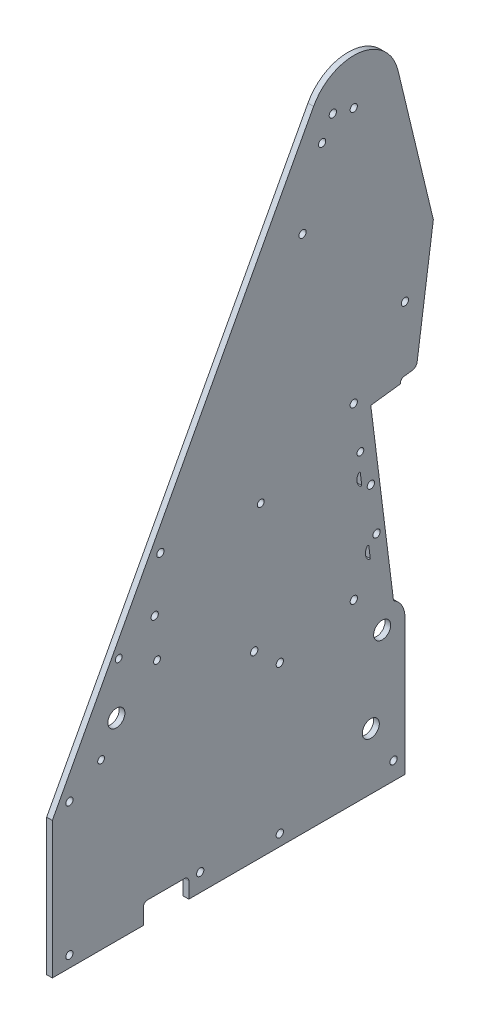
SolidWorks part; units mm, degrees
ref_plane "Front Plane" through (0, 0, 0) normal (0, 0, 1) x (1, 0, 0)
ref_plane "Top Plane" through (0, 0, 0) normal (0, 1, 0) x (1, 0, 0)
ref_plane "Right Plane" through (0, 0, 0) normal (1, 0, 0) x (0, 0, -1)
sketch "Sketch1" plane through (0, 0, 0) normal (1, 0, 0) x (0, 0, -1)
  line L0 (0, 0) -> (0, 76.2)
  line L6 (-19.05, 188.0016) -> (-2.512, 190.0852)
  line L7 (6.4943, 193.62) -> (15.875, 260.35)
  line L8 (15.875, 260.35) -> (-3.8791, 342.4892)
  line L9 (-50.965, 348.5436) -> (-196.85, 76.2)
  line L10 (-196.85, 0) -> (0, 0)
  line L11 (-196.85, 76.2) -> (-196.85, 0)
  line L12 (-19.05, 188.0016) -> (-6.35, 87.1985)
  line L13 (-0.4471, 192.7455) -> (6.4943, 193.62)
  line L14 (-2.512, 190.0852) -> (-3.1086, 194.8203) construction
  line L15 (-2.512, 190.0852) -> (6.1508, 191.1766) construction
  line L16 (6.1508, 191.1766) -> (6.4943, 193.62) construction
  arc A0 (-3.8791, 342.4892) -> (-50.965, 348.5436) centre (-28.575, 336.55) ccw
  arc A3 (0, 76.2) -> (-6.35, 87.1985) centre (-12.7, 76.2) ccw
  arc A4 (-2.512, 190.0852) -> (-0.4471, 192.7455) centre (-0.1494, 190.3829) cw
  dimension "D2" = 25.4
  dimension "D6" = 196.85
  dimension "D7" = 76.2
  dimension "D12" = 12.7
  dimension "D8" = 19.05
  dimension "D10" = 2.3813
  dimension "D1" = 28.575
  dimension "D3" = 336.55
  dimension "D4" = 25.4
  dimension "D5" = 101.6
  dimension "D9" = 6.35
  dimension ".5" = 12.7
  dimension "D11" = 76.2
  dimension "D13" = 76.2
  dimension "D14" = 15.875
  dimension "D15" = 6.35
extrude "Boss-Extrude1" add sketch "Sketch1" along normal blind 3.175
sketch "Sketch2" plane through (3.175, 0, 0) normal (1, 0, 0) x (0, 0, -1)
  line L16 (-146.05, 8.7909) -> (-146.05, -0.3034) construction
  line L17 (-123.0376, 11.1785) -> (-143.6624, 11.1785) construction
  line L18 (-120.65, -0.3034) -> (-120.65, 8.7909) construction
  line L19 (-146.05, 8.7909) -> (-146.05, 0)
  line L20 (-123.0376, 11.1785) -> (-143.6624, 11.1785)
  line L21 (-120.65, 0) -> (-120.65, 8.7909)
  line L25 (-146.05, 0) -> (-120.65, 0)
  line L26 (-196.85, 0) -> (0, 0) construction
  line L33 (-223.2996, 0) -> (-223.2996, 6.35) construction
  line L34 (-229.6496, 0) -> (-223.2996, 0) construction
  line L35 (-229.6496, 6.35) -> (-229.6496, 0) construction
  line L36 (-223.2996, 6.35) -> (-229.6496, 6.35) construction
  line L37 (-223.2996, 0) -> (-223.2996, 6.35)
  line L38 (-229.6496, 0) -> (-223.2996, 0)
  line L39 (-229.6496, 6.35) -> (-229.6496, 0)
  line L40 (-223.2996, 6.35) -> (-229.6496, 6.35)
  arc A0 (-143.6624, 11.1785) -> (-146.05, 8.7909) centre (-143.6624, 8.7909) ccw construction
  arc A1 (-120.65, 8.7909) -> (-123.0376, 11.1785) centre (-123.0376, 8.7909) ccw construction
  arc A2 (-143.6624, 11.1785) -> (-146.05, 8.7909) centre (-143.6624, 8.7909) ccw
  arc A3 (-120.65, 8.7909) -> (-123.0376, 11.1785) centre (-123.0376, 8.7909) ccw
extrude "Cut-Extrude1" cut sketch "Sketch2" against normal through all
sketch "Sketch3" plane through (3.175, 0, 0) normal (1, 0, 0) x (0, 0, -1)
  point P4 (-12.7, 76.2)
hole_wizard "3/8 Clearance Hole1" positions "Sketch3" profile "Sketch4" hole size "3/8" standard "ANSI Inch" end condition up to next
sketch "Sketch4" plane through (3.175, 76.2, 12.7) normal (0, 1, 0) x (0, 0, -1)
  line L0 (0, 0) -> (0, 3.175)
  line L1 (0, 3.175) -> (4.7625, 3.175)
  line L2 (4.7625, 3.175) -> (4.7625, 0)
  line L5 (4.7625, 0) -> (0, 0)
  line L11 (0, -6.35) -> (0, 107.95) construction
  dimension "Thru Hole Dia." = 9.525
  dimension "Thru Hole Depth" = 3.175
sketch "Sketch5" plane through (3.175, 0, 0) normal (1, 0, 0) x (0, 0, -1)
  line L0 (-12.7, 76.2) -> (19.6681, 37.0472)
  line L1 (19.6681, 37.0472) -> (18.4836, 24.56)
  line L2 (15.6221, 41.9413) -> (-25.2806, 17.5464)
  line L3 (-15.875, 19.05) -> (-25.2806, 17.5464)
  line L4 (0, 0) -> (0, 76.2) construction
  line L5 (-15.875, 19.05) -> (-27.0501, 3.6221)
  line L6 (-27.0501, 3.6221) -> (-54.7505, 169.5016)
  line L7 (50.8, 0) -> (50.8, 73.5762) construction
  dimension "D1" = 44.45
  dimension "D2" = 50.8
  dimension "D3" = 45
  dimension "D4" = 60.325
  dimension "D5" = 19.05
  dimension "D6" = 15.875
  dimension "D7" = 9.525
  dimension "D8" = 47.625
  dimension "D9" = 19.05
  dimension "D10" = 45
  dimension "D11" = 50.8
sketch "Sketch6" plane through (3.175, 0, 0) normal (1, 0, 0) x (0, 0, -1)
  circle A3 centre (-161.1018, 107.8367) radius 4.7625
  circle A5 centre (-161.1018, 107.8367) radius 6.985 construction
  circle A8 centre (-159.7995, 135.9536) radius 1.905 construction
  circle A9 centre (-138.417, 124.4998) radius 1.905 construction
  arc A10 (-167.9472, 91.0243) -> (-168.7477, 93.563) centre (-169.6472, 91.8837) ccw construction
  arc A11 (-168.7477, 93.563) -> (-171.3047, 92.8228) centre (-169.6472, 91.8837) ccw construction
  arc A12 (-171.3047, 92.8228) -> (-167.9472, 91.0243) centre (-169.6472, 91.8837) ccw construction
  circle A17 centre (-159.7995, 135.9536) radius 1.905
  circle A18 centre (-138.417, 124.4998) radius 1.905
  arc A19 (-167.9472, 91.0243) -> (-168.7477, 93.563) centre (-169.6472, 91.8837) ccw
  arc A20 (-168.7477, 93.563) -> (-171.3047, 92.8228) centre (-169.6472, 91.8837) ccw
  arc A21 (-171.3047, 92.8228) -> (-167.9472, 91.0243) centre (-169.6472, 91.8837) ccw
  dimension "D1" = 9.525
extrude "Cut-Extrude2" cut sketch "Sketch6" against normal through all
sketch "Sketch10" plane through (3.175, 0, 0) normal (1, 0, 0) x (0, 0, -1)
  circle A0 centre (-71.2566, 151.9429) radius 2.032
  dimension "D1" = 4.064
sketch "Sketch11" plane through (3.175, 0, 0) normal (1, 0, 0) x (0, 0, -1)
  circle A0 centre (-187.325, 80.5336) radius 2.032
  circle A1 centre (-187.325, 6.35) radius 2.032
  circle A2 centre (-187.325, 6.35) radius 2.032 construction
  circle A3 centre (-187.325, 80.5336) radius 2.032 construction
  dimension "D1" = 4.064
extrude "Cut-Extrude5" cut sketch "Sketch11" against normal through all
sketch "Sketch13" plane through (0, 0, 0) normal (-1, 0, 0) x (0, 0, 1)
  circle A0 centre (40.2353, 339.6611) radius 2.032
  circle A1 centre (46.232, 328.466) radius 2.032
  circle A2 centre (40.2353, 339.6611) radius 1.905 construction
  circle A3 centre (46.232, 328.466) radius 1.905 construction
  dimension "D1" = 4.064
extrude "Cut-Extrude6" cut sketch "Sketch13" against normal through all
sketch "Sketch14" plane through (3.175, 0, 0) normal (1, 0, 0) x (0, 0, -1)
  line L0 (-50.965, 348.5436) -> (-196.85, 76.2) construction
  line L1 (-136.525, 175.369) -> (-142.1225, 178.3674) construction
  circle A0 centre (-136.525, 175.369) radius 2.032
  dimension "D1" = 4.064
  dimension "D2" = 6.35
  dimension "D3" = 136.525
extrude "Cut-Extrude7" cut sketch "Sketch14" against normal through all
sketch "Sketch15" plane through (3.175, 0, 0) normal (1, 0, 0) x (0, 0, -1)
  circle A0 centre (-19.05, 31.75) radius 4.7625
  circle A1 centre (-12.7, 76.2) radius 4.7625 construction
  circle A2 centre (-28.575, 193.675) radius 2.032
  dimension "D1" = 44.45
  dimension "D3" = 4.064
  dimension "D2" = 6.35
  dimension "D4" = 161.925
  dimension "D5" = 9.525
extrude "Cut-Extrude8" cut sketch "Sketch15" against normal through all
sketch "Sketch16" plane through (3.175, 0, 0) normal (1, 0, 0) x (0, 0, -1)
  line L0 (-24.978, 158.8539) -> (-24.0851, 151.7662)
  line L1 (-6.35, 87.1985) -> (-19.05, 188.0016) construction
  line L2 (-20.2155, 121.0527) -> (-21.0031, 120.9535)
  line L3 (-24.978, 158.8539) -> (-25.7656, 158.7547)
  line L4 (-24.0851, 151.7662) -> (-24.8726, 151.667)
  line L5 (-12.7, 137.6001) -> (-26.6484, 135.8427) construction
  line L6 (-19.3226, 113.965) -> (-20.1101, 113.8658)
  line L7 (-19.3226, 113.965) -> (-20.2155, 121.0527)
  line L8 (-25.3253, 161.6102) -> (-23.7378, 149.0099) construction
  arc A0 (-25.7656, 158.7547) -> (-24.8726, 151.667) centre (-21.7352, 155.6624) ccw
  arc A1 (-20.1101, 113.8658) -> (-21.0031, 120.9535) centre (-16.9727, 117.8612) cw
  circle A2 centre (-19.0126, 149.6052) radius 2.032
  circle A3 centre (-15.8376, 124.4044) radius 2.032
  point P2 (-24.5315, 155.31)
  dimension "D2" = 0.7937
  dimension "D3" = 5.08
  dimension "D5" = 4.064
  dimension "D1" = 7.1437
  dimension "D4" = 38.1
  dimension "D6" = 4.7625
  dimension "D7" = 25.4
extrude "Cut-Extrude9" cut sketch "Sketch16" against normal up to next
fillet "Fillet1" radius 3.175 1 edges at (1.5875, 193.62, -6.4943)
sketch "Sketch17" plane through (3.175, 0, 0) normal (1, 0, 0) x (0, 0, -1)
  circle A0 centre (-6.35, 9.9085) radius 2.032
  circle A1 centre (-69.85, 6.35) radius 2.032
  circle A2 centre (-114.3, 9.9085) radius 2.032
  circle A3 centre (-114.3, 9.9085) radius 1.905 construction
  circle A4 centre (-69.85, 6.35) radius 2.286 construction
  circle A5 centre (-6.35, 9.9085) radius 1.905 construction
  dimension "D1" = 4.064
extrude "Cut-Extrude10" cut sketch "Sketch17" against normal through all
sketch "Sketch18" plane through (0, 0, 0) normal (-1, 0, 0) x (0, 0, 1)
  line L0 (50.965, 348.5436) -> (196.85, 76.2) construction
  circle A0 centre (0, 228.6) radius 2.032
  circle A1 centre (69.85, 88.9) radius 2.032
  circle A2 centre (139.7, 146.5801) radius 2.032
  circle A3 centre (57.15, 289.9291) radius 2.032
  dimension "D1" = 4.064
  dimension "D2" = 228.6
  dimension "D4" = 17.145
  dimension "D5" = 139.7
  dimension "D6" = 22.225
  dimension "D7" = 57.15
  dimension "D8" = 69.85
  dimension "D9" = 88.9
extrude "Cut-Extrude11" cut sketch "Sketch18" against normal through all
sketch "Sketch19" plane through (0, 0, 0) normal (-1, 0, 0) x (0, 0, 1)
  circle A0 centre (28.575, 336.55) radius 2.032
  arc A1 (50.965, 348.5436) -> (3.8791, 342.4892) centre (28.575, 336.55) ccw construction
  dimension "D1" = 4.064
extrude "Cut-Extrude12" cut sketch "Sketch19" against normal through all
sketch "Sketch20" plane through (3.175, 0, 0) normal (1, 0, 0) x (0, 0, -1)
  line L0 (-84.1375, 101.6) -> (-28.5243, 98.6854) construction
  line L1 (-84.1375, 101.6) -> (-84.1375, 99.4903) construction
  circle A0 centre (-28.5243, 98.6854) radius 2.032
  circle A1 centre (-84.1375, 101.6) radius 2.032
  dimension "D2" = 4.064
  dimension "D1" = 55.6895
  dimension "D3" = 87
  dimension "D4" = 84.1375
  dimension "D5" = 101.6
extrude "Cut-Extrude13" cut sketch "Sketch20" against normal through all
sketch "Sketch22" plane through (3.175, 0, 0) normal (1, 0, 0) x (0, 0, -1)
  circle A0 centre (-80.4818, 171.3543) radius 1.905
  circle A1 centre (-24.8687, 168.4397) radius 1.905
  dimension "D1" = 3.81
extrude "Cut-Extrude14" cut sketch "Sketch22" against normal blind 6.35
